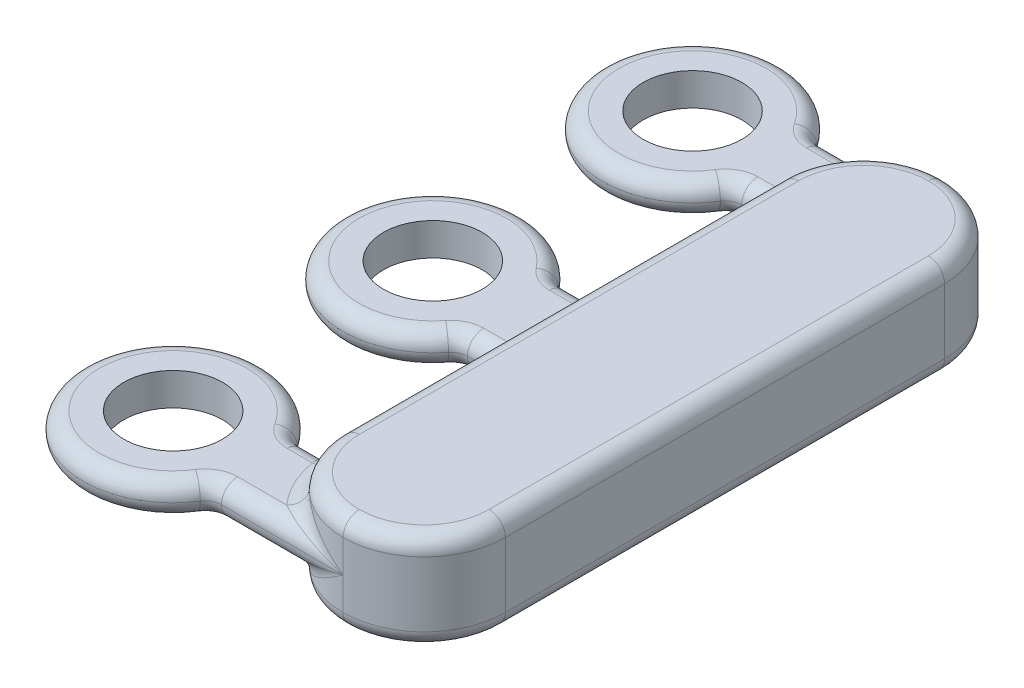
SolidWorks part; units mm, degrees
ref_plane "Alzado" through (0, 0, 0) normal (0, 0, 1) x (1, 0, 0)
ref_plane "Planta" through (0, 0, 0) normal (0, 1, 0) x (1, 0, 0)
ref_plane "Vista lateral" through (0, 0, 0) normal (1, 0, 0) x (0, 0, -1)
sketch "Croquis2" plane through (0, 0, 0) normal (0, 1, 0) x (1, 0, 0)
  line L0 (0, 0) -> (11, 0) construction
  line L1 (11, -16) -> (11, 16) construction
  line L2 (11, 16) -> (0, 16) construction
  line L3 (11, -16) -> (0, -16) construction
  line L4 (8, -13.5) -> (4.9438, -13.5)
  line L5 (17.1329, 18.5317) -> (4.9277, 18.5317)
  line L7 (8, 13.5) -> (4.9438, 13.5)
  line L9 (17.1329, 18.5317) -> (4.9438, 13.5) construction
  line L10 (16.9083, 13.5367) -> (4.9277, 18.5317) construction
  line L12 (8, -13.5) -> (8, -3.0218)
  line L15 (8, -13.5) -> (14, 13.5) construction
  line L16 (8, 13.5) -> (14, -13.5) construction
  line L18 (17.1329, -18.5317) -> (4.9277, -18.5317)
  line L20 (8, 3.0218) -> (8, 13.5)
  line L21 (8, -3.0218) -> (4.6433, -3.0218)
  line L23 (8, 3.0218) -> (4.6433, 3.0218)
  line L25 (8.5049, -3.0216) -> (4.6433, 3.0218) construction
  line L26 (8.4772, 2.9783) -> (4.6433, -3.0218) construction
  line L27 (17.1329, 18.5317) -> (18, 18.5317)
  line L28 (18, 18.5317) -> (18, -18.5317)
  line L29 (18, -18.5317) -> (17.1329, -18.5317)
  circle A0 centre (0, 0) radius 3.04
  arc A1 (4.6433, 3.0218) -> (4.6433, -3.0218) centre (0, 0) ccw
  circle A2 centre (0, 16) radius 3.04
  arc A3 (4.9277, 18.5317) -> (4.9438, 13.5) centre (0, 16) ccw
  circle A4 centre (0, -16) radius 3.04
  arc A5 (4.9277, -18.5317) -> (4.9438, -13.5) centre (0, -16) cw
  circle A7 centre (0, 0) radius 5.54 construction
  point P9 (11, 0)
  point P27 (6.5742, 0)
  point P32 (5.5, 0)
  dimension "D1" = 6.08
  dimension "D5" = 6.08
  dimension "D6" = 2.5
  dimension "D8" = 11
  dimension "D3" = 11
  dimension "D4" = 32
  dimension "D7" = 5
  dimension "D9" = 6
  dimension "D10" = 6
  dimension "D11" = 10
  dimension "D2" = 2.5
extrude "Saliente-Extruir1" add sketch "Croquis2" along normal mid plane 2
sketch "Croquis4" plane through (0, 0, 0) normal (0, 1, 0) x (1, 0, 0)
  line L0 (4.9277, -18.5317) -> (18, -18.5317) construction
  line L1 (18, 18.5317) -> (8, 18.5317)
  line L2 (18, 18.5317) -> (18, -18.5317)
  line L3 (18, -18.5317) -> (8, -18.5317)
  line L4 (8, 18.5317) -> (8, -18.5317)
  dimension "D1" = 10
extrude "Saliente-Extruir2" add sketch "Croquis4" along normal mid plane 6
fillet "Redondeo1" radius 5 6 edges at (18, 0, -18.5317) (18, 0, 18.5317) (8, -2, -18.5317) (8, 2, -18.5317) (8, -2, 18.5317) (8, 2, 18.5317)
fillet "Redondeo4" radius 1 18 edges at (6.4719, 1, 13.5) (6.4719, -1, 13.5) (8.9639, 1, 18.5317) (8.9639, -1, 18.5317) (8.9639, 1, -18.5317) (8.9639, -1, -18.5317) (6.4719, 1, -13.5) (6.4719, -1, -13.5) (6.3216, 1, -3.0218) (6.3216, -1, -3.0218) (6.3216, 1, 3.0218) (6.3216, -1, 3.0218) (-5.54, 1, 15.9822) (-5.54, -1, 15.9822) (-5.54, 1, -15.9822) (-5.54, -1, -15.9822) (-5.54, 1, 0) (-5.54, -1, 0)
fillet "Redondeo5" radius 1 22 edges at (10.7916, -0.874, -18.0175) (8.7666, -1, -16.1922) (8.0135, -0.7989, -13.8985) (8.0122, 0.7855, -13.8811) (10.7916, 0.874, -18.0175) (8, 0.7071, 2.7289) (8, -0.7071, 2.7289) (8, -1, 0) (8, -0.7071, -2.7289) (8, 0.7071, -2.7289) (10.7916, 0.874, 18.0175) (10.7916, -0.874, 18.0175) (8.7666, -1, 16.1922) (8.0122, -0.7855, 13.8811) (8.0135, 0.7989, 13.8985) (8.7666, 1, -16.1922) (8, 1, 0) (8.7666, 1, 16.1922) (8, -0.1258, -13.5079) (8, 0.1258, -13.5079) (8, -0.1258, 13.5079) (8, 0.1258, 13.5079)
fillet "Redondeo6" radius 1 12 edges at (16.5355, 3, 17.0672) (9.4645, 3, 17.0672) (8, 3, 0) (9.4645, 3, -17.0672) (16.5355, 3, -17.0672) (18, 3, 0) (8, -3, 0) (9.4645, -3, 17.0672) (16.5355, -3, 17.0672) (18, -3, 0) (16.5355, -3, -17.0672) (9.4645, -3, -17.0672)
